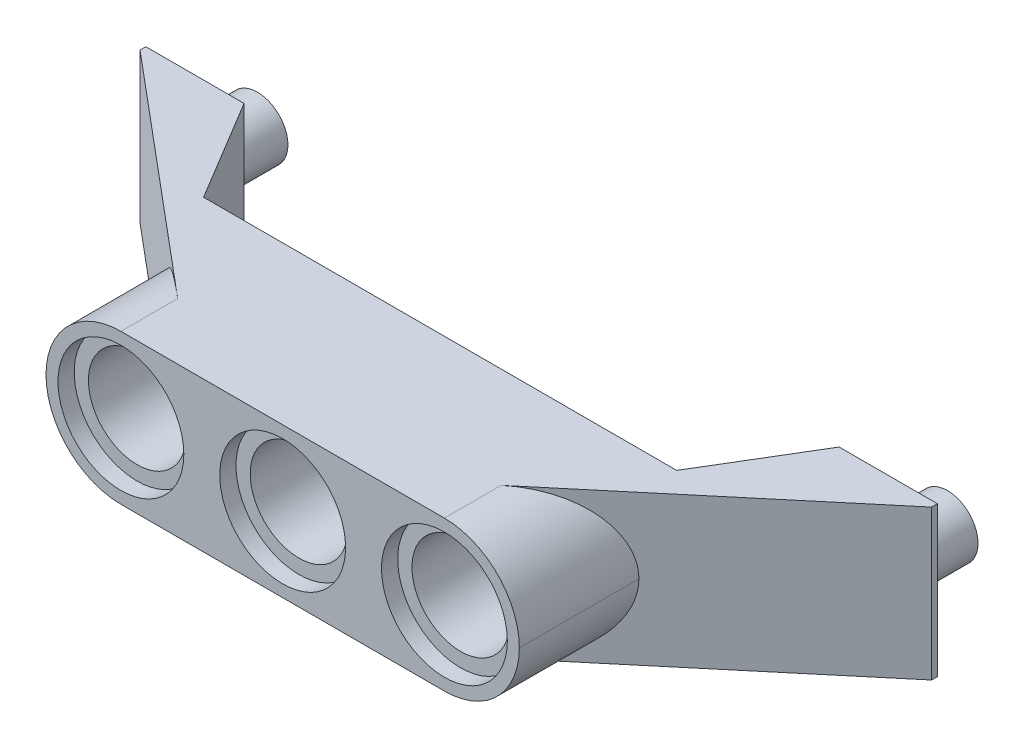
SolidWorks part; units mm, degrees
ref_plane "Front Plane" through (0, 0, 0) normal (0, 0, 1) x (1, 0, 0)
ref_plane "Top Plane" through (0, 0, 0) normal (0, 1, 0) x (1, 0, 0)
ref_plane "Right Plane" through (0, 0, 0) normal (1, 0, 0) x (0, 0, -1)
sketch "Sketch1" plane through (0, 0, 0) normal (0, 0, 1) x (1, 0, 0)
  line L1 (-11.4525, 5.6362) -> (11.8675, 5.6362)
  line L2 (-11.4525, 5.6362) -> (-11.4525, -1.7438)
  line L3 (-11.4525, -1.7438) -> (11.8675, -1.7438)
  line L4 (11.8675, 5.6362) -> (11.8675, -1.7438)
  dimension "D1" = 23.32
  dimension "D2" = 7.38
extrude "Boss-Extrude1" add sketch "Sketch1" along normal blind 7.76
sketch "Sketch2" plane through (0, 0, 7.76) normal (0, 0, 1) x (1, 0, 0)
  line L0 (11.8675, -1.7438) -> (11.8675, 5.6362) construction
  line L1 (11.8675, 5.6362) -> (-11.4525, 5.6362) construction
  circle A0 centre (-7.7625, 1.9462) radius 2.4
  circle A1 centre (0.2075, 1.9462) radius 2.4
  circle A2 centre (8.1775, 1.9462) radius 2.4
  dimension "D4" = 4.8
  dimension "D5" = 4.8
  dimension "D6" = 4.8
  dimension "D1" = 3.69
  dimension "D2" = 7.97
  dimension "D3" = 7.97
  dimension "D7" = 3.69
  dimension "D8" = 3.69
  dimension "D9" = 3.69
sketch "Sketch4" plane through (0, 0, 7.76) normal (0, 0, 1) x (1, 0, 0)
  circle A2 centre (0.2075, 1.9462) radius 2.4
  circle A3 centre (8.1775, 1.9462) radius 2.4
  circle A4 centre (-7.7625, 1.9462) radius 2.4
  point P10 (-10.1625, 1.9462)
  point P11 (-7.7625, 1.9462)
  dimension "D1" = 0
  dimension "D2" = 4.8
extrude "Cut-Extrude1" cut sketch "Sketch4" against normal blind 7.76
sketch "Sketch5" plane through (0, 0, 7.76) normal (0, 0, 1) x (1, 0, 0)
  circle A0 centre (-7.7625, 1.9462) radius 3.1
  circle A1 centre (0.2075, 1.9462) radius 3.1
  circle A2 centre (8.1775, 1.9462) radius 3.1
  dimension "D1" = 6.2
  dimension "D2" = 6.2
  dimension "D3" = 6.2
extrude "Cut-Extrude2" cut sketch "Sketch5" against normal blind 0.8
sketch "Sketch6" plane through (0, 0, 0) normal (0, 0, -1) x (-1, 0, 0)
  circle A0 centre (-8.1775, 1.9462) radius 3.1
  circle A1 centre (-0.2075, 1.9462) radius 3.1
  circle A2 centre (7.7625, 1.9462) radius 3.1
  dimension "D1" = 6.2
  dimension "D2" = 6.2
  dimension "D3" = 6.2
extrude "Cut-Extrude3" cut sketch "Sketch6" against normal blind 0.8
sketch "Sketch7" plane through (11.8675, 0, 0) normal (1, 0, 0) x (0, 0, -1)
  line L0 (0, -1.7438) -> (0, 5.6362) construction
  line L1 (0, 5.6362) -> (-2, 5.6362)
  line L2 (0, 5.6362) -> (0, -1.7438)
  line L3 (0, -1.7438) -> (-2, -1.7438)
  line L4 (-2, 5.6362) -> (-2, -1.7438)
  line L5 (-7.76, 5.6362) -> (0, 5.6362) construction
  line L6 (-7.76, -1.7438) -> (0, -1.7438) construction
  dimension "D1" = 0
  dimension "D2" = 0
  dimension "D3" = 2
extrude "Boss-Extrude2" add sketch "Sketch7" along normal blind 7.84
sketch "Sketch8" plane through (-11.4525, 0, 0) normal (-1, 0, 0) x (0, 0, 1)
  line L0 (7.76, 5.6362) -> (0, 5.6362) construction
  line L1 (0, -1.7438) -> (2, -1.7438)
  line L2 (0, -1.7438) -> (0, 5.6362)
  line L3 (0, 5.6362) -> (2, 5.6362)
  line L4 (2, -1.7438) -> (2, 5.6362)
  dimension "D1" = 2
extrude "Boss-Extrude3" add sketch "Sketch8" along normal blind 7.84
sketch "Sketch9" plane through (0, 0, 0) normal (0, 0, -1) x (-1, 0, 0)
  line L0 (-19.7075, 5.6362) -> (19.2925, 5.6362) construction
  line L1 (-19.7075, -1.7438) -> (-11.8675, -1.7438)
  line L2 (-19.7075, -1.7438) -> (-19.7075, 5.6362)
  line L3 (-19.7075, 5.6362) -> (-11.8675, 5.6362)
  line L4 (-11.8675, -1.7438) -> (-11.8675, 5.6362)
  line L6 (19.2925, -1.7438) -> (11.4525, -1.7438)
  line L7 (19.2925, -1.7438) -> (19.2925, 5.6362)
  line L8 (19.2925, 5.6362) -> (11.4525, 5.6362)
  line L9 (11.4525, -1.7438) -> (11.4525, 5.6362)
  dimension "D1" = 7.84
  dimension "D2" = 7.84
extrude "Boss-Extrude4" add sketch "Sketch9" along normal blind 5
sketch "Sketch10" plane through (0, 0, -5) normal (0, 0, -1) x (-1, 0, 0)
  line L0 (19.2925, -1.7438) -> (19.2925, 5.6362) construction
  line L1 (19.2925, 5.6362) -> (11.4525, 5.6362) construction
  line L2 (-11.8675, 5.6362) -> (-19.7075, 5.6362) construction
  line L3 (-19.7075, 5.6362) -> (-19.7075, -1.7438) construction
  circle A0 centre (16.7925, 1.9462) radius 1.5
  circle A1 centre (-17.2075, 1.9462) radius 1.5
  dimension "D2" = 3.69
  dimension "D3" = 3
  dimension "D4" = 3.69
  dimension "D6" = 3
  dimension "D1" = 2.5
  dimension "D5" = 2.5
extrude "Boss-Extrude5" add sketch "Sketch10" along normal blind 3
chamfer "Chamfer1" distance 8 angle 40 1 edges at (19.7075, 1.9462, 2) first distance on face at (15.7875, 1.9462, 2)
chamfer "Chamfer2" distance 8 angle 40 1 edges at (-19.2925, 1.9462, 2) first distance on face at (-15.3725, 1.9462, 2)
chamfer "Chamfer3" distance 3 angle 59 1 edges at (11.8675, 1.9462, -5) first distance on face at (18.7075, 1.9462, -5)
chamfer "Chamfer4" distance 3 angle 59 1 edges at (-11.4525, 1.9462, -5) first distance on face at (-18.2925, 1.9462, -5)
fillet "Fillet1" radius 3.69 4 edges at (11.8675, -1.7438, 4.8129) (11.8675, 5.6362, 4.8129) (-11.4525, 5.6362, 4.8129) (-11.4525, -1.7438, 4.8129)
